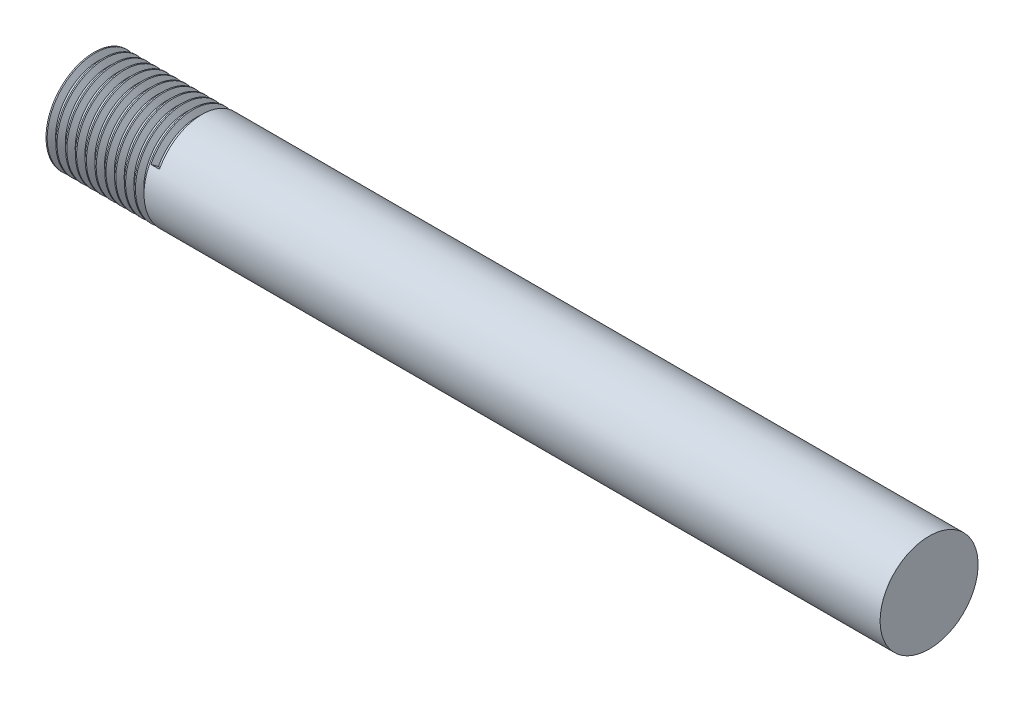
SolidWorks part; units mm, degrees
ref_plane "Front Plane" through (0, 0, 0) normal (0, 0, 1) x (1, 0, 0)
ref_plane "Top Plane" through (0, 0, 0) normal (0, 1, 0) x (1, 0, 0)
ref_plane "Right Plane" through (0, 0, 0) normal (1, 0, 0) x (0, 0, -1)
sketch "Sketch1" plane through (0, 0, 0) normal (0, 0, 1) x (1, 0, 0)
  line L0 (0, 0) -> (0, 6.35)
  line L1 (0, 6.35) -> (108.5625, 6.35)
  line L4 (108.5625, 6.35) -> (108.5625, 0)
  line L5 (108.5625, 0) -> (0, 0)
  line L6 (-315.9627, 0) -> (15482.1706, 0) construction
  point P3 (108.5625, 6.4397)
  dimension "D1" = 12.7
  dimension "D3" = 108.5625
revolve "Revolve1" add sketch "Sketch1" angle 360 about L6
thread "Thread1" pitch 1.27 method cut profile "Thread Profile1" start angle 0, offset 1.27, length 14.5, pitch 1.27, diameter 12.7
ref_plane "Plane1" through (-1.27, 0, -6.35) normal (0, -1, 0) x (0, 0, -1)
sketch "Thread Profile1" plane through (-1.27, 0, -6.35) normal (0, -1, 0) x (0, 0, -1)
  line L0 (0, 0) -> (0, 1.27) construction
  line L11 (0, 0) -> (0, 1.1112)
  line L12 (0, 1.1112) -> (-0.6874, 0.7144)
  line L13 (-0.6874, 0.7144) -> (-0.6874, 0.3969)
  line L15 (-0.6874, 0.3969) -> (0, 0)
  line L17 (-0.6874, 0.5556) -> (0, 0.5556) construction
  point P2 (0, 0)
  dimension "Pitch" = 1.27
  dimension "Profile_Angle" = 60
  dimension "Profile_Land" = 0.3175
  dimension "Profile_Height" = 0.6874
